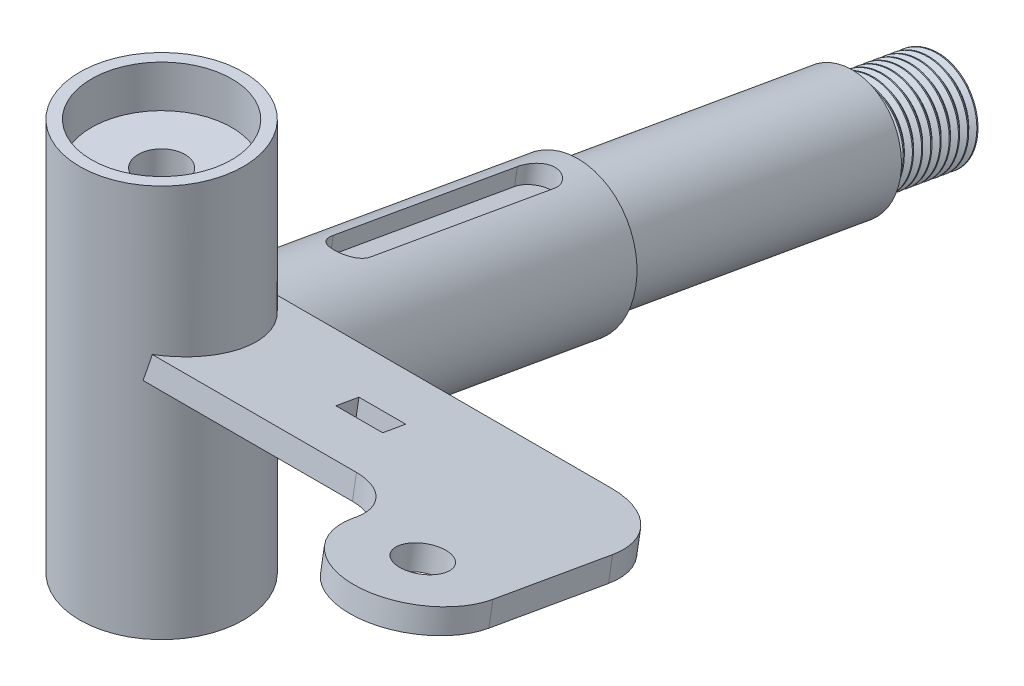
SolidWorks part; units mm, degrees
material "EN8"
ref_plane "Front Plane" through (0, 0, 0) normal (0, 0, 1) x (1, 0, 0)
ref_plane "Top Plane" through (0, 0, 0) normal (0, 1, 0) x (1, 0, 0)
ref_plane "Right Plane" through (0, 0, 0) normal (1, 0, 0) x (0, 0, -1)
sketch "Sketch2" plane through (0, 0, 0) normal (1, 0, 0) x (0, 0, -1)
  line L4 (0, 42) -> (0, -42) construction
  line L5 (0, 0) -> (5, 0) construction
  line L6 (5, 33) -> (15, 33)
  line L7 (15, 33) -> (15, 42)
  line L8 (15, 42) -> (17.5, 42)
  line L9 (17.5, 42) -> (17.5, -42)
  line L10 (17.5, -42) -> (15, -42)
  line L11 (15, -42) -> (15, -33)
  line L12 (15, -33) -> (5, -33)
  line L14 (0, -42) -> (15, -42) construction
  line L15 (0, 42) -> (15, 42) construction
  line L17 (5, 0) -> (17.5, 0) construction
  line L18 (5, -33) -> (5, 33)
  point P4 (0, 0)
  point P22 (5, 0)
  dimension "D1" = 84
  dimension "D2" = 15
  dimension "D3" = 5
  dimension "D4" = 9
  dimension "D5" = 17.5
  dimension "D6" = 15
revolve "Revolve4" add sketch "Sketch2" angle 360 about L4
sketch "Sketch5" plane through (0, 0, 0) normal (1, 0, 0) x (0, 0, -1)
  line L0 (0, 0) -> (-35, 0) construction
  line L1 (-35, 0) -> (-45, 0) construction
  line L2 (-45, 0) -> (-53, 0) construction
  line L3 (-53, 0) -> (17.5, -12.4311) construction
  line L4 (-53, 25) -> (-53, -25)
  line L5 (-57.3412, -24.6202) -> (-48.6588, 24.6202)
  line L6 (13.1588, -37.0512) -> (21.8412, 12.1891)
  line L7 (17.5, -42) -> (17.5, 42) construction
  line L8 (17.5, -42) -> (17.5, 42)
  point P8 (-53, 0)
  point P11 (-53, 0)
  point P17 (17.5, -12.4311)
  dimension "D1" = 35
  dimension "D2" = 10
  dimension "D3" = 8
  dimension "D4" = 50
  dimension "D5" = 10
ref_plane "Plane1" through (0, -3.3675, -19.0981) normal (0, -0.1736, -0.9848) x (0, 0.9848, -0.1736)
sketch "Sketch6" plane through (0, -3.3675, -19.0981) normal (0, -0.1736, -0.9848) x (0, 0.9848, -0.1736)
  circle A0 centre (-9.2034, 0) radius 15
  dimension "D1" = 30
extrude "Boss-Extrude1" add sketch "Sketch6" along normal blind 70
sketch "Sketch7" plane through (0, -15.5229, -88.0347) normal (0, -0.1736, -0.9848) x (-1, 0, 0)
  circle A2 centre (0, -9.2034) radius 12.5
  circle A3 centre (0, -9.2034) radius 12.5
  dimension "D1" = 2.5
extrude "Boss-Extrude2" add sketch "Sketch7" along normal blind 60
sketch "Sketch8" plane through (0, -25.9418, -147.1232) normal (0, -0.1736, -0.9848) x (-1, 0, 0)
  circle A2 centre (0, -9.2034) radius 10
  circle A3 centre (0, -9.2034) radius 10
  dimension "D1" = 2.5
extrude "Boss-Extrude3" add sketch "Sketch8" along normal blind 20
sketch "Sketch10" plane through (0, -3.3675, -19.0981) normal (0, 0.1736, 0.9848) x (1, 0, 0)
  arc A1 (8.4153, -21.6204) -> (-8.4153, -21.6204) centre (0, -9.2034) ccw
  arc A2 (8.4153, -21.6204) -> (-8.4153, -21.6204) centre (0, -9.2034) ccw
  ellipse E1 centre (0, -109.9818) end of major axis (0, -9.2034) minor radius 17.5 (8.4153, -21.6204) -> (-8.4153, -21.6204) ccw
  ellipse E2 centre (0, -109.9818) end of major axis (0, -9.2034) minor radius 17.5 (8.4153, -21.6204) -> (-8.4153, -21.6204) ccw
  dimension "D1" = 0
extrude "Boss-Extrude4" add sketch "Sketch10" along normal up to surface up to face at (0, -42, 17.5)
thread "Thread1" pitch 2 method cut profile "Thread Profile1" start angle 0, offset 3, length 0, pitch 2, diameter 20
ref_plane "Plane2" through (10, -38.9992, -168.1756) normal (0, -0.9848, 0.1736) x (1, 0, 0)
sketch "Thread Profile1" plane through (10, -38.9992, -168.1756) normal (0, -0.9848, 0.1736) x (1, 0, 0)
  line L0 (0, 0) -> (0, 2) construction
  line L11 (0, 0) -> (0, 1.75)
  line L12 (0, 1.75) -> (-1.0825, 1.125)
  line L13 (-1.0825, 1.125) -> (-1.0825, 0.625)
  line L15 (-1.0825, 0.625) -> (0, 0)
  line L17 (-1.0825, 0.875) -> (0, 0.875) construction
  point P2 (0, 0)
  dimension "Pitch" = 2
  dimension "Profile_Angle" = 60
  dimension "Profile_Land" = 0.5
  dimension "Profile_Height" = 1.0825
sketch "Sketch20" plane through (0, 0, 0) normal (1, 0, 0) x (0, 0, -1)
  line L0 (0, 42) -> (0, -42)
  line L1 (0, -42) -> (0, 42) construction
  line L2 (-17.5, -42) -> (17.5, -42) construction
  line L3 (17.5, 42) -> (-17.5, 42) construction
  line L4 (86.4365, -24.5864) -> (0, -9.3453)
  line L5 (84.2659, -36.8965) -> (88.6071, -12.2763) construction
  dimension "D1" = 100
sketch "Sketch21" plane through (0, 0, 0) normal (0, 0, 1) x (1, 0, 0)
  line L0 (0, -9.3453) -> (-50, -9.3453)
  line L1 (0, 42) -> (0, -42) construction
  line L2 (0, -24.5864) -> (0, -9.3453) construction
  dimension "D1" = 50
  dimension "D2" = 9.3453
ref_plane "Plane4" through (0, -9.0635, 1.5981) normal (0, -0.9848, 0.1736) x (-1, 0, 0)
ref_plane "Plane5" through (0, 5.7086, -1.0066) normal (0, -0.9848, 0.1736) x (-1, 0, 0)
sketch "Sketch26" plane through (0, 5.7086, -1.0066) normal (0, -0.9848, 0.1736) x (-1, 0, 0)
  line L0 (0, 0) -> (-80, 0) construction
  line L1 (-80, 0) -> (-80, -25.9936) construction
  line L2 (-80, -25.9936) -> (0, 0) construction
  line L3 (-95, 0) -> (-95, -25.9936)
  line L4 (-65, -25.9936) -> (-65, -15)
  line L5 (-65, -15) -> (-80, -15)
  line L6 (-80, 15) -> (-80, -15)
  circle A0 centre (-80, -25.9936) radius 5
  arc A1 (-95, -25.9936) -> (-65, -25.9936) centre (-80, -25.9936) ccw
  arc A2 (-80, 15) -> (-95, 0) centre (-80, 0) ccw
  circle A4 centre (-80, -25.9936) radius 15 construction
  point P7 (-105, -38.9904)
  dimension "D3" = 10
  dimension "D1" = 80
  dimension "D2" = 18
  dimension "D4" = 10
extrude "Boss-Extrude5" add sketch "Sketch26" against normal mid plane 5 separate body
sketch "Sketch27" plane through (80, 0, 0) normal (-1, 0, 0) x (0, 0, 1)
  line L4 (-15.3446, 0.6418) -> (14.1997, 5.8513)
  line L5 (14.1997, 5.8513) -> (13.3314, 10.7753)
  line L6 (13.3314, 10.7753) -> (-16.2128, 5.5659)
  line L7 (-16.2128, 5.5659) -> (-15.3446, 0.6418)
  line L8 (-15.3446, 0.6418) -> (14.1997, 5.8513)
  line L9 (14.1997, 5.8513) -> (13.3314, 10.7753)
  line L10 (13.3314, 10.7753) -> (-16.2128, 5.5659)
  line L11 (-16.2128, 5.5659) -> (-15.3446, 0.6418)
  dimension "D1" = 0
extrude "Boss-Extrude6" add sketch "Sketch27" along normal up to surface (68.6632 mm away) up to face at (0, 42, 17.5)
fillet "Fillet1" radius 10 1 edges at (65, 8.3133, 13.7655)
sketch "Sketch28" plane through (0, 8.1706, -1.4407) normal (0, 0.9848, -0.1736) x (1, 0, 0)
  line L0 (43.2937, 15) -> (43.2937, -15) construction
  line L1 (6.5875, 15) -> (80, 15) construction
  line L2 (11.3368, -15) -> (55, -15) construction
  line L3 (8.2937, 0) -> (78.2937, 0) construction
  line L5 (3.2937, 2.5) -> (13.2937, 2.5)
  line L6 (3.2937, 2.5) -> (3.2937, -2.5)
  line L7 (3.2937, -2.5) -> (13.2937, -2.5)
  line L8 (13.2937, 2.5) -> (13.2937, -2.5)
  line L9 (3.2937, 2.5) -> (13.2937, -2.5) construction
  line L10 (3.2937, -2.5) -> (13.2937, 2.5) construction
  line L11 (38.2937, 2.5) -> (48.2937, 2.5)
  line L12 (38.2937, 2.5) -> (38.2937, -2.5)
  line L13 (38.2937, -2.5) -> (48.2937, -2.5)
  line L14 (48.2937, 2.5) -> (48.2937, -2.5)
  line L15 (38.2937, 2.5) -> (48.2937, -2.5) construction
  line L16 (38.2937, -2.5) -> (48.2937, 2.5) construction
  point P9 (43.2937, 0)
  point P13 (43.2937, 0)
  dimension "D1" = 70
  dimension "D2" = 10
  dimension "D3" = 5
extrude "Cut-Extrude2" cut sketch "Sketch28" against normal blind 10
sketch "Sketch29" plane through (0, 5.7086, -1.0066) normal (0, -0.9848, 0.1736) x (-1, 0, 0)
  line L0 (12.5, 89.3928) -> (-12.5, 89.3928) construction
  line L2 (0, 89.3928) -> (0, 31.3928) construction
  line L3 (0, 80.3928) -> (0, 40.3928) construction
  line L4 (4, 80.3928) -> (4, 40.3928)
  line L5 (-4, 80.3928) -> (-4, 40.3928)
  arc A0 (4, 80.3928) -> (-4, 80.3928) centre (0, 80.3928) ccw
  arc A1 (-4, 40.3928) -> (4, 40.3928) centre (0, 40.3928) ccw
  point P3 (0, 84.3928)
  point P8 (0, 60.3928)
  dimension "D1" = 4
  dimension "D2" = 40
  dimension "D3" = 5
extrude "Cut-Extrude3" cut sketch "Sketch29" along normal mid plane 8
sketch "Sketch30" plane through (0, 5.7086, -1.0066) normal (0, -0.9848, 0.1736) x (-1, 0, 0)
  line L0 (0, 89.3928) -> (0, 74.3928) construction
  line L1 (15, 89.3928) -> (-15, 89.3928) construction
  line L2 (0, 74.3928) -> (0, 54.3928) construction
  circle A0 centre (0, 74.3928) radius 3
  circle A1 centre (0, 54.3928) radius 3
  dimension "D1" = 6
  dimension "D2" = 20
  dimension "D3" = 15
extrude "Cut-Extrude4" cut sketch "Sketch30" against normal blind 8 from offset 30
